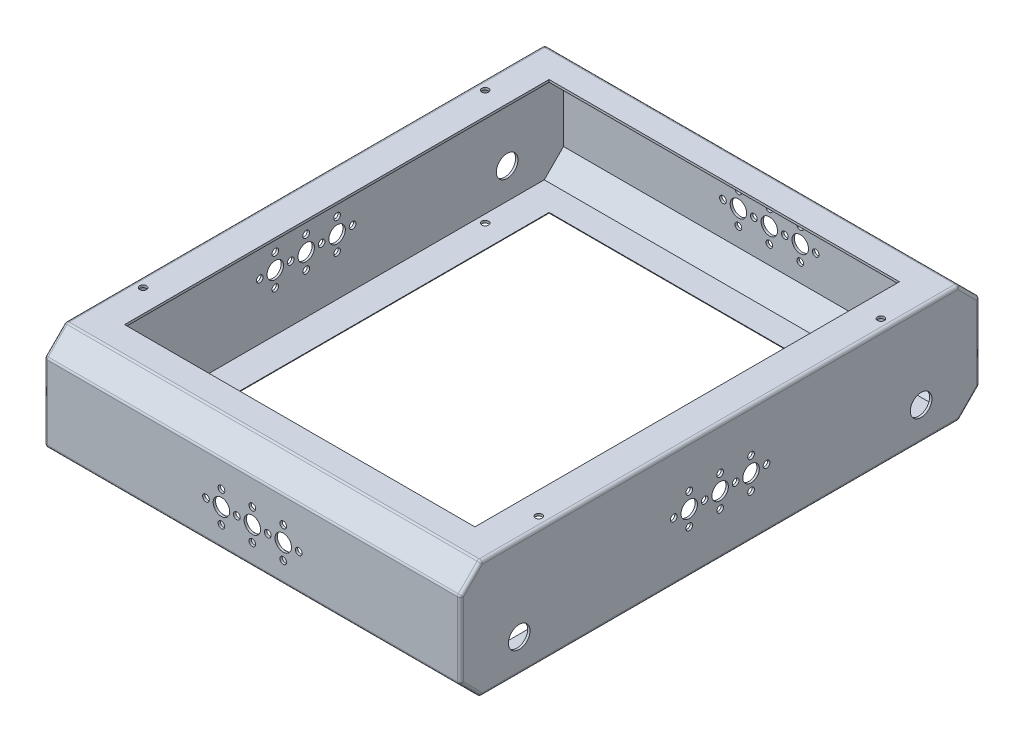
SolidWorks part; units mm, degrees
material "6063-T1"
ref_plane "Front Plane" through (0, 0, 0) normal (0, 0, 1) x (1, 0, 0)
ref_plane "Top Plane" through (0, 0, 0) normal (0, 1, 0) x (1, 0, 0)
ref_plane "Right Plane" through (0, 0, 0) normal (1, 0, 0) x (0, 0, -1)
sketch "Sketch1" plane through (0, 0, 0) normal (1, 0, 0) x (0, 0, -1)
  line L1 (0, 0) -> (252, 0)
  line L2 (0, 0) -> (0, 57)
  line L3 (0, 57) -> (252, 57)
  line L4 (252, 0) -> (252, 57)
  dimension "D1" = 252
  dimension "D2" = 57
extrude "Boss-Extrude1" add sketch "Sketch1" along normal blind 202
sketch "Sketch2" plane through (0, 0, 0) normal (-1, 0, 0) x (0, 0, 1)
  line L0 (-252, 47) -> (-242, 57)
  line L1 (-252, 0) -> (-252, 57) construction
  line L2 (-252, 57) -> (0, 57) construction
  line L3 (-252, 47) -> (-252, 57)
  line L4 (-252, 57) -> (-242, 57)
  line L5 (-1252, 28.5) -> (48748, 28.5) construction
  line L6 (-126, -943) -> (-126, 49057) construction
  line L7 (-252, 10) -> (-252, 0)
  line L8 (-252, 10) -> (-242, 0)
  line L9 (-252, 0) -> (-242, 0)
  line L10 (0, 10) -> (-10, 0)
  line L11 (0, 0) -> (-10, 0)
  line L12 (0, 10) -> (0, 0)
  line L13 (0, 47) -> (0, 57)
  line L14 (0, 47) -> (-10, 57)
  line L15 (0, 57) -> (-10, 57)
  point P11 (-252, 28.5)
  point P15 (-126, 57)
  dimension "D1" = 10
extrude "Cut-Extrude1" cut sketch "Sketch2" against normal through all
sketch "Sketch3" plane through (0, 0, 0) normal (0, -1, 0) x (1, 0, 0)
  line L0 (0, -10) -> (0, -242) construction
  line L1 (16, -23) -> (186, -23)
  line L2 (16, -23) -> (16, -229)
  line L3 (16, -229) -> (186, -229)
  line L4 (186, -23) -> (186, -229)
  line L5 (202, -10) -> (202, -242) construction
  line L6 (202, -10) -> (0, -10) construction
  line L8 (202, -242) -> (0, -242) construction
  dimension "D1" = 170
  dimension "D2" = 206
  dimension "D3" = 16
  dimension "D4" = 16
  dimension "D5" = 13
  dimension "D6" = 13
extrude "Cut-Extrude2" cut sketch "Sketch3" against normal through all
shell "Shell3" thickness 1.14 removed face at (101, 28.5, -229) removed face at (16, 28.5, -126) removed face at (186, 28.5, -126) removed face at (101, 28.5, -23)
sketch "Sketch4" plane through (202, 0, 0) normal (1, 0, 0) x (0, 0, -1)
  line L0 (0, 47) -> (0, 10) construction
  line L2 (10, 0) -> (242, 0) construction
  circle A0 centre (126, 28.5) radius 4
  circle A1 centre (141, 28.5) radius 4
  circle A2 centre (111, 28.5) radius 4
  circle A3 centre (126, 36) radius 1.625
  circle A4 centre (126, 21) radius 1.625
  circle A5 centre (133.5, 28.5) radius 1.625
  circle A6 centre (141, 21) radius 1.625
  circle A7 centre (148.5, 28.5) radius 1.625
  circle A8 centre (118.5, 28.5) radius 1.625
  circle A9 centre (103.5, 28.5) radius 1.625
  circle A10 centre (111, 36) radius 1.625
  circle A11 centre (111, 21) radius 1.625
  circle A12 centre (141, 36) radius 1.625
  point P9 (0, 28.5)
  point P13 (126, 0)
  dimension "D1" = 8
  dimension "D4" = 3.25
  dimension "D5" = 7.5
  dimension "D6" = 7.5
  dimension "D7" = 7.5
  dimension "D8" = 7.5
  dimension "D9" = 7.5
  dimension "D10" = 7.5
  dimension "D2" = 15
  dimension "D3" = 15
extrude "Cut-Extrude3" cut sketch "Sketch4" against normal through all
sketch "Sketch5" plane through (0, 0, 0) normal (0, 0, 1) x (1, 0, 0)
  line L1 (202, 10) -> (0, 10) construction
  circle A0 centre (101, 26.875) radius 4
  circle A1 centre (116, 26.875) radius 4
  circle A2 centre (86, 26.875) radius 4
  circle A3 centre (101, 34.375) radius 1.625
  circle A4 centre (101, 19.375) radius 1.625
  circle A5 centre (108.5, 26.875) radius 1.625
  circle A6 centre (116, 19.375) radius 1.625
  circle A7 centre (123.5, 26.875) radius 1.625
  circle A8 centre (93.5, 26.875) radius 1.625
  circle A9 centre (78.5, 26.875) radius 1.625
  circle A10 centre (86, 34.375) radius 1.625
  circle A11 centre (86, 19.375) radius 1.625
  circle A12 centre (116, 34.375) radius 1.625
  point P31 (101, 10)
  dimension "D1" = 8
  dimension "D4" = 3.25
  dimension "D2" = 15
  dimension "D3" = 15
  dimension "D5" = 7.5
  dimension "D6" = 7.5
  dimension "D7" = 7.5
  dimension "D8" = 7.5
  dimension "D9" = 7.5
  dimension "D10" = 7.5
extrude "Cut-Extrude4" cut sketch "Sketch5" against normal through all
sketch "Sketch6" plane through (202, 0, 0) normal (1, 0, 0) x (0, 0, -1)
  line L0 (242, 57) -> (10, 57) construction
  line L1 (0, 47) -> (0, 10) construction
  line L2 (126, -943) -> (126, 49057) construction
  line L3 (10, 0) -> (242, 0) construction
  circle A0 centre (28.5, 16) radius 5.25
  circle A1 centre (223.5, 16) radius 5.25
  point P9 (126, 57)
  dimension "D1" = 10.5
  dimension "D2" = 16
  dimension "D3" = 28.5
extrude "Cut-Extrude5" cut sketch "Sketch6" against normal through all
fillet "Fillet1" radius 1.5 28 edges at (202, 57, -126) (0, 57, -126) (101, 10, 0) (202, 5, -5) (0, 5, -5) (101, 57, -10) (202, 52, -5) (101, 47, 0) (0, 52, -5) (0, 0, -126) (101, 0, -10) (202, 0, -126) (186, 0, -126) (101, 0, -23) (16, 0, -126) (101, 0, -229) (101, 0, -242) (202, 5, -247) (101, 10, -252) (0, 5, -247) (101, 47, -252) (202, 52, -247) (101, 57, -242) (0, 52, -247) (202, 28.5, 0) (0, 28.5, 0) (0, 28.5, -252) (202, 28.5, -252)
sketch "Sketch7" plane through (0, 57, 0) normal (0, 1, 0) x (1, 0, 0)
  line L0 (16, 229) -> (186, 229) construction
  line L1 (0, 10.6213) -> (0, 241.3787) construction
  line L2 (202, 241.3787) -> (202, 10.6213) construction
  line L4 (186, 23) -> (16, 23) construction
  circle A0 centre (5, 209) radius 1.65
  circle A1 centre (197, 209) radius 1.65
  circle A2 centre (197, 43) radius 1.65
  circle A3 centre (5, 43) radius 1.65
  dimension "D1" = 3.3
  dimension "D2" = 20
  dimension "D3" = 5
  dimension "D4" = 5
  dimension "D5" = 20
extrude "Cut-Extrude6" cut sketch "Sketch7" against normal through all
